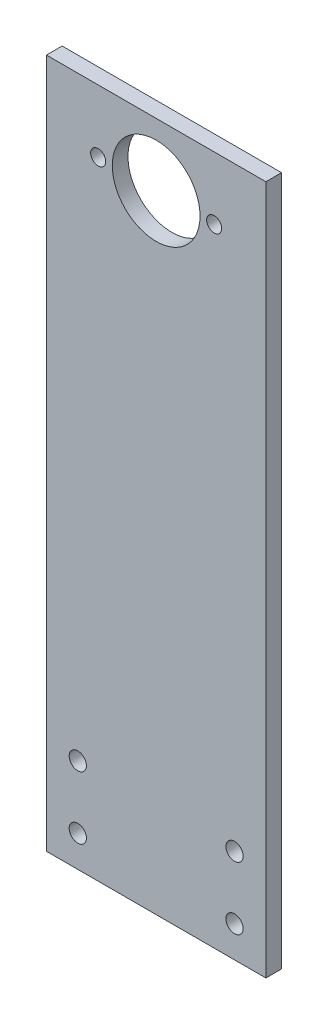
SolidWorks part; units mm, degrees
ref_plane "Front Plane" through (0, 0, 0) normal (0, 0, 1) x (1, 0, 0)
ref_plane "Top Plane" through (0, 0, 0) normal (0, 1, 0) x (1, 0, 0)
ref_plane "Right Plane" through (0, 0, 0) normal (1, 0, 0) x (0, 0, -1)
sketch "Sketch1" plane through (0, 0, 0) normal (0, 0, 1) x (1, 0, 0)
  line L0 (0, 0) -> (0, 100) construction
  line L1 (-35, -100) -> (35, -100) construction
  line L2 (-35, -100) -> (-35, 100)
  line L3 (-35, 100) -> (35, 100)
  line L4 (35, -100) -> (35, 100)
  line L5 (-35, -100) -> (35, 100) construction
  line L6 (-35, 100) -> (35, -100) construction
  line L7 (-18.5, 80) -> (18.5, 80) construction
  line L8 (0, 0) -> (0, -100) construction
  line L9 (-25, -90) -> (25, -90) construction
  line L10 (-35, -100) -> (-35, -120)
  line L11 (56.9327, -120) -> (-643.0673, -120) construction
  line L12 (-35, -120) -> (35, -120)
  line L13 (35, -120) -> (35, -100)
  circle A0 centre (-18.5, 80) radius 2.4
  circle A1 centre (18.5, 80) radius 2.4
  circle A2 centre (0, 80) radius 5
  circle A3 centre (-25, -90) radius 2.75
  circle A4 centre (25, -90) radius 2.75
  circle A5 centre (25, -110) radius 2.75
  circle A6 centre (-25, -110) radius 2.75
  circle A7 centre (0, 80) radius 14
  point P0 (0, 0)
  point P10 (0, 80)
  point P18 (0, -90)
  dimension "D4" = 4.8
  dimension "D5" = 10
  dimension "D6" = 5.5
  dimension "D11" = 28
  dimension "D1" = 70
  dimension "D2" = 200
  dimension "D3" = 37
  dimension "D7" = 10
  dimension "D8" = 20
  dimension "D9" = 10
  dimension "D10" = 20
extrude "Boss-Extrude1" add sketch "Sketch1" along normal blind 5 contours L12 L13 L4 L3 L2 L10 A7 A6 A5 A4 A3 A1 A0 region at (0, -13.4206, 0)
